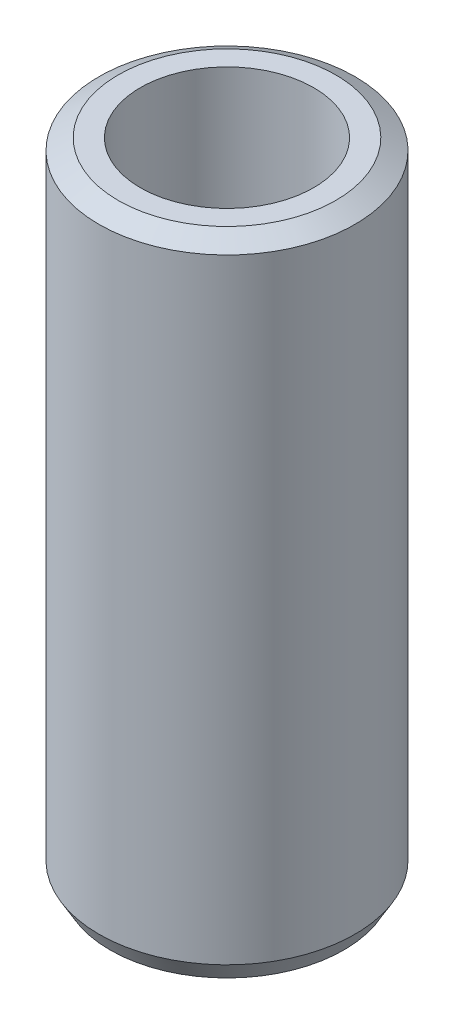
SolidWorks part; units mm, degrees
ref_plane "Front Plane" through (0, 0, 0) normal (0, 0, 1) x (1, 0, 0)
ref_plane "Top Plane" through (0, 0, 0) normal (0, 1, 0) x (1, 0, 0)
ref_plane "Right Plane" through (0, 0, 0) normal (1, 0, 0) x (0, 0, -1)
sketch "Sketch1" plane through (0, 0, 0) normal (0, 1, 0) x (1, 0, 0)
  circle A0 centre (0, 0) radius 57.5
  dimension "SHAFT_OD" = 115
extrude "Boss-Extrude1" add sketch "Sketch1" along normal blind 289.7585
sketch "Sketch2" plane through (0, 0, 0) normal (0, 1, 0) x (1, 0, 0)
  circle A0 centre (0, 0) radius 38.9491
  dimension "BORE_D" = 77.8981
extrude "Cut-Extrude1" cut sketch "Sketch2" along normal through all
chamfer "Chamfer1" distance 4.9853 angle 60 2 edges at (0, 289.7585, 57.5) (0, 0, 57.5) first distance on face at (0, 289.7585, 57.5) first distance on face at (0, 0, 38.9491)
